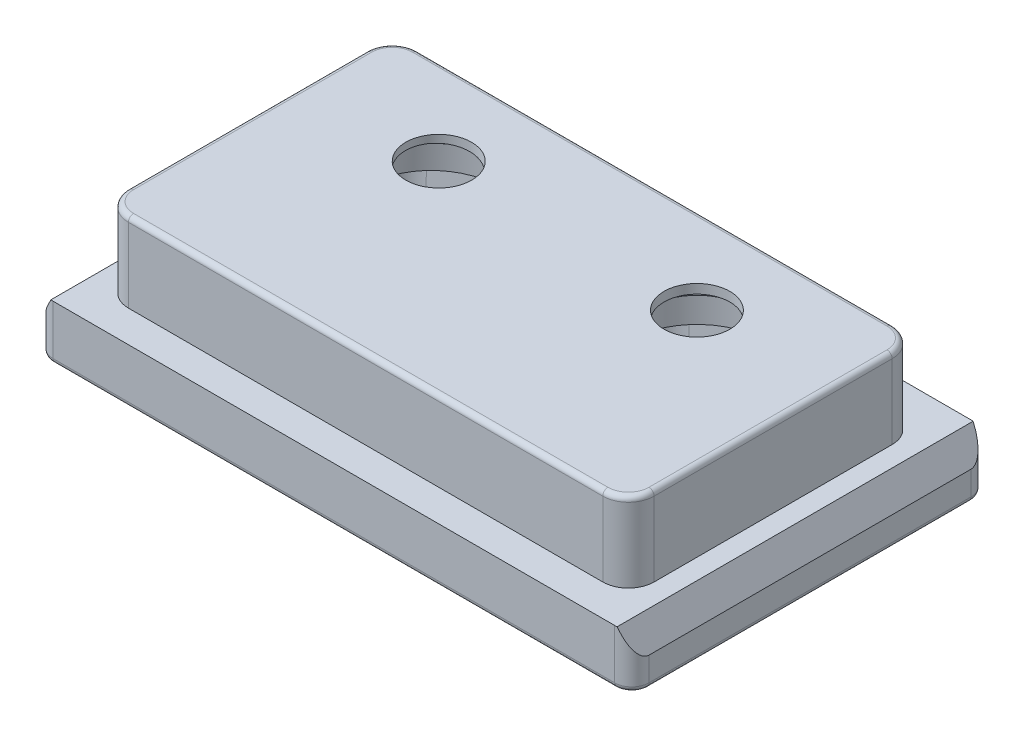
SolidWorks part; units mm, degrees
ref_plane "Front Plane" through (0, 0, 0) normal (0, 0, 1) x (1, 0, 0)
ref_plane "Top Plane" through (0, 0, 0) normal (0, 1, 0) x (1, 0, 0)
ref_plane "Right Plane" through (0, 0, 0) normal (1, 0, 0) x (0, 0, -1)
sketch "Sketch1" plane through (0, 0, 0) normal (0, 1, 0) x (1, 0, 0)
  line L1 (41.656, -26.416) -> (-41.656, -26.416)
  line L2 (44.196, -23.876) -> (44.196, 23.876)
  line L3 (41.656, 26.416) -> (-41.656, 26.416)
  line L4 (-44.196, -23.876) -> (-44.196, 23.876)
  line L5 (44.196, -26.416) -> (-44.196, 26.416) construction
  line L6 (44.196, 26.416) -> (-44.196, -26.416) construction
  arc A0 (-41.656, -26.416) -> (-44.196, -23.876) centre (-41.656, -23.876) cw
  arc A1 (41.656, -26.416) -> (44.196, -23.876) centre (41.656, -23.876) ccw
  arc A2 (44.196, 23.876) -> (41.656, 26.416) centre (41.656, 23.876) ccw
  arc A3 (-41.656, 26.416) -> (-44.196, 23.876) centre (-41.656, 23.876) ccw
  point P0 (0, 0)
  dimension "D3" = 2.54
  dimension "D1" = 52.832
  dimension "D2" = 88.392
extrude "Boss-Extrude1" add sketch "Sketch1" along normal blind 8.128
fillet "Fillet1" radius 0.762 8 edges at (-43.4521, 0, 25.6721) (-44.196, 0, 0) (-43.4521, 0, -25.6721) (0, 0, -26.416) (43.4521, 0, -25.6721) (44.196, 0, 0) (43.4521, 0, 25.6721) (0, 0, 26.416)
chamfer "Chamfer1" distance 3.81 angle 30 2 edges at (44.196, 8.128, 0) (-44.196, 8.128, 0) tangent propagation no first distance on face at (44.196, 4.445, 0) first distance on face at (-44.196, 4.445, 0)
sketch "Sketch2" plane through (0, 8.128, 0) normal (0, 1, 0) x (1, 0, 0)
  line L0 (44.196, 23.876) -> (44.196, -23.876) construction
  line L1 (-35.179, 21.209) -> (35.179, 21.209)
  line L2 (-38.989, 17.399) -> (-38.989, -17.907)
  line L3 (-35.179, -21.717) -> (35.179, -21.717)
  line L4 (38.989, 17.399) -> (38.989, -17.907)
  line L5 (-41.656, -26.416) -> (41.656, -26.416) construction
  arc A0 (35.179, 21.209) -> (38.989, 17.399) centre (35.179, 17.399) cw
  arc A1 (35.179, -21.717) -> (38.989, -17.907) centre (35.179, -17.907) ccw
  arc A2 (-38.989, -17.907) -> (-35.179, -21.717) centre (-35.179, -17.907) ccw
  arc A3 (-35.179, 21.209) -> (-38.989, 17.399) centre (-35.179, 17.399) ccw
  dimension "D5" = 3.81
  dimension "D1" = 42.926
  dimension "D2" = 77.978
  dimension "D3" = 5.207
  dimension "D4" = 4.699
extrude "Boss-Extrude2" add sketch "Sketch2" along normal blind 11.7856
fillet "Fillet2" radius 0.762 8 edges at (-38.989, 19.9136, 0.254) (-37.8731, 19.9136, -20.0931) (0, 19.9136, -21.209) (37.8731, 19.9136, -20.0931) (38.989, 19.9136, 0.254) (37.8731, 19.9136, 20.6011) (0, 19.9136, 21.717) (-37.8731, 19.9136, 20.6011)
sketch "Sketch3" plane through (0, 8.128, 0) normal (0, 1, 0) x (1, 0, 0)
  line L0 (-38.989, 17.399) -> (-38.989, -17.907) construction
  line L1 (-38.989, -9.5758) -> (-40.513, -9.5758)
  line L2 (-38.989, -9.5758) -> (-38.989, 8.5598)
  line L3 (-38.989, 8.5598) -> (-40.513, 8.5598)
  line L4 (-40.513, -9.5758) -> (-40.513, 8.5598)
  line L5 (35.179, 21.209) -> (-35.179, 21.209) construction
  dimension "D1" = 1.524
  dimension "D3" = 18.1356
  dimension "D2" = 12.6492
extrude "Boss-Extrude3" add sketch "Sketch3" along normal blind 6.35
sketch "Sketch4" plane through (0, 14.478, 0) normal (0, 1, 0) x (1, 0, 0)
  line L0 (-40.513, 8.5598) -> (-40.513, -9.5758) construction
  line L1 (-38.989, -9.5758) -> (-38.989, 8.5598) construction
  line L2 (-41.9963, -9.5758) -> (-41.9963, 8.5598) construction
  line L3 (-41.9963, 26.3931) -> (-41.9963, -26.3931) construction
  line L4 (-38.989, -9.5758) -> (-40.513, -9.5758)
  line L5 (-40.513, -9.5758) -> (-40.513, 8.5598)
  line L6 (-40.513, 8.5598) -> (-38.989, 8.5598)
  arc A0 (-38.989, 8.5598) -> (-40.513, 5.9438) centre (-41.9963, 8.5598) cw
  arc A1 (-38.989, -9.5758) -> (-40.513, -6.9598) centre (-41.9963, -9.5758) ccw
  line M3 (-38.989, 8.5598) -> (-40.513, 8.5598)
  line M4 (-40.513, 8.5598) -> (-40.513, -9.5758)
  line M5 (-40.513, -9.5758) -> (-38.989, -9.5758)
  dimension "D1" = 0
extrude "Cut-Extrude1" cut sketch "Sketch4" against normal up to surface (6.35 mm away) contours A1 M5 M4 | A0 M3 M4 region at (-39.8879, 14.478, -7.5344) region at (-39.8879, 14.478, 8.5504) up to face at (0, 8.128, 0)
fillet "Fillet3" radius 0.508 2 edges at (-40.513, 11.303, -5.9438) (-40.513, 11.303, 6.9598)
sketch "Sketch5" plane through (0, 0, 0) normal (0, -1, 0) x (1, 0, 0)
  line L0 (44.196, 23.876) -> (44.196, -23.876) construction
  line L1 (-32.385, -23.749) -> (32.385, -23.749)
  line L2 (-41.275, -14.859) -> (-41.275, 14.859)
  line L3 (-32.385, 23.749) -> (32.385, 23.749)
  line L4 (41.275, -14.859) -> (41.275, 14.859)
  line L6 (41.656, -26.416) -> (-41.656, -26.416) construction
  arc A0 (32.385, 23.749) -> (41.275, 14.859) centre (32.385, 14.859) cw
  arc A1 (32.385, -23.749) -> (41.275, -14.859) centre (32.385, -14.859) ccw
  arc A2 (-41.275, 14.859) -> (-32.385, 23.749) centre (-32.385, 14.859) cw
  arc A3 (-32.385, -23.749) -> (-41.275, -14.859) centre (-32.385, -14.859) cw
  point P12 (41.275, -23.749)
  point P17 (-41.275, -23.749)
  dimension "D5" = 8.89
  dimension "D1" = 82.55
  dimension "D2" = 2.921
  dimension "D3" = 47.498
  dimension "D4" = 2.667
extrude "Cut-Extrude2" cut sketch "Sketch5" against normal blind 3.048
fillet "Fillet4" radius 0.254 8 edges at (0, 0, -23.749) (-38.6712, 0, -21.1452) (-41.275, 0, 0) (-38.6712, 0, 21.1452) (0, 0, 23.749) (38.6712, 0, 21.1452) (41.275, 0, 0) (38.6712, 0, -21.1452)
sketch "Sketch6" plane through (0, 3.048, 0) normal (0, -1, 0) x (1, 0, 0)
  line L0 (44.196, -23.876) -> (44.196, 23.876) construction
  line L1 (41.656, -26.416) -> (-41.656, -26.416) construction
  circle A0 centre (0, -18.161) radius 1.1303
  circle A1 centre (0, 18.161) radius 1.1303
  circle A2 centre (-35.687, 2.159) radius 1.1303
  circle A3 centre (35.687, 2.159) radius 1.1303
  dimension "D7" = 2.2606
  dimension "D8" = 2.2606
  dimension "D9" = 2.2606
  dimension "D10" = 2.2606
  dimension "D1" = 35.687
  dimension "D2" = 35.687
  dimension "D3" = 8.509
  dimension "D4" = 20.32
  dimension "D5" = 16.002
  dimension "D6" = 8.255
extrude "Cut-Extrude3" cut sketch "Sketch6" against normal blind 10.16
sketch "Sketch7" plane through (0, 19.9136, 0) normal (0, 1, 0) x (1, 0, 0)
  line L0 (-35.179, 21.209) -> (35.179, 21.209) construction
  line L1 (38.989, 17.399) -> (38.989, -17.907) construction
  circle A0 centre (19.05, 8.382) radius 4.8768
  dimension "D3" = 9.7536
  dimension "D1" = 12.827
  dimension "D2" = 19.939
extrude "Cut-Extrude4" cut sketch "Sketch7" against normal through all
ref_plane "Plane1" through (-19.2532, 0, 0) normal (1, 0, 0) x (0, 0, -1)
ref_axis "Axis1" through (-19.2532, 19.9136, 20.955) along (0, 0, -1)
ref_plane "Plane2" through (0.9413, 18.9083, 0) normal (0.0497, 0.9988, 0) x (0, 0, -1)
sketch "Sketch8" plane through (0.9413, 18.9083, 0) normal (0.0497, 0.9988, 0) x (0, 0, -1)
  line L0 (21.209, 36.0877) -> (21.209, -34.1832) construction
  line L1 (-20.955, 20.2195) -> (20.447, 20.2195) construction
  circle A0 centre (8.382, 20.2195) radius 4.8768
  dimension "D3" = 9.7536
  dimension "D1" = 12.827
  dimension "D2" = 0
extrude "Cut-Extrude5" cut sketch "Sketch8" against normal through all and the other way blind 10.16
ref_plane "Plane3" through (0.4879, 9.8009, 0) normal (0.0497, 0.9988, 0) x (0, 0, -1)
sketch "Sketch9" plane through (0.4879, 9.8009, 0) normal (0.0497, 0.9988, 0) x (0, 0, -1)
  line L0 (3.5558, 5.4049) -> (-8.7689, 12.5206)
  line L1 (16.129, 35.4595) -> (5.1433, 35.4595)
  line L2 (19.304, 32.2845) -> (19.304, 8.1545)
  line L3 (16.129, 4.9795) -> (5.1433, 4.9795)
  line L4 (5.1433, 4.9795) -> (3.4419, 4.9795) construction
  line L5 (3.5558, 35.0341) -> (-8.7689, 27.9185)
  line L6 (3.5558, 5.4049) -> (4.2926, 4.9795) construction
  line L7 (5.1433, 35.4595) -> (3.8888, 35.4595) construction
  line L8 (3.5558, 35.0341) -> (4.2926, 35.4595) construction
  circle A0 centre (8.382, 20.2195) radius 4.8768 construction
  arc A1 (-8.7689, 27.9185) -> (-8.7689, 12.5206) centre (-4.3239, 20.2195) ccw
  arc A2 (3.5558, 35.0341) -> (5.1433, 35.4595) centre (5.1433, 32.2845) cw
  arc A3 (3.5558, 5.4049) -> (5.1433, 4.9795) centre (5.1433, 8.1545) ccw
  arc A4 (19.304, 8.1545) -> (16.129, 4.9795) centre (16.129, 8.1545) cw
  arc A5 (16.129, 35.4595) -> (19.304, 32.2845) centre (16.129, 32.2845) cw
  dimension "D6" = 8.89
  dimension "D5" = 3.175
  dimension "D1" = 30.48
  dimension "D2" = 15.24
  dimension "D3" = 10.922
  dimension "D4" = 15.0114
  dimension "D7" = 60
  dimension "D8" = 30
  dimension "D9" = 15.0114
extrude "Cut-Extrude6" cut sketch "Sketch9" against normal blind 10.16
sketch "Sketch10" plane through (0.4879, 9.8009, 0) normal (-0.0497, -0.9988, 0) x (0.9988, -0.0497, 0)
  circle A0 centre (-20.2195, -8.382) radius 6.8326
  dimension "D1" = 13.6652
extrude "Cut-Extrude7" cut sketch "Sketch10" against normal blind 7.7724
sketch "Sketch11" plane through (0.4879, 9.8009, 0) normal (-0.0497, -0.9988, 0) x (0.9988, -0.0497, 0)
  circle A0 centre (-20.2195, -8.382) radius 7.2517
  dimension "D1" = 14.5034
extrude "Cut-Extrude8" cut sketch "Sketch11" against normal blind 6.7818
sketch "Sketch12" plane through (0.4879, 9.8009, 0) normal (-0.0497, -0.9988, 0) x (0.9988, -0.0497, 0)
  circle A0 centre (-20.2195, -8.382) radius 9.2329
  dimension "D1" = 18.4658
extrude "Cut-Extrude9" cut sketch "Sketch12" against normal blind 5.9436
sketch "Sketch13" plane through (0.4879, 9.8009, 0) normal (-0.0497, -0.9988, 0) x (0.9988, -0.0497, 0)
  circle A0 centre (-20.2195, -8.382) radius 10.3632
  dimension "D1" = 20.7264
extrude "Cut-Extrude10" cut sketch "Sketch13" against normal blind 4.953
fillet "Fillet5" radius 0.254 2 edges at (-10.1896, 16.2835, -8.382) (-12.496, 18.2293, -8.382)
sketch "Sketch14" plane through (0, 3.048, 0) normal (0, -1, 0) x (1, 0, 0)
  line L0 (19.05, -8.382) -> (19.05, 4.5223) construction
  line L1 (6.985, -19.304) -> (31.115, -19.304)
  line L2 (3.81, -16.129) -> (3.81, -5.1323)
  line L3 (3.81, -4.2926) -> (34.29, -4.2926)
  line L4 (34.29, -16.129) -> (34.29, -5.1323)
  line L5 (11.3222, 8.917) -> (4.2251, -3.5627)
  line L6 (26.7778, 8.917) -> (33.8749, -3.5627)
  circle A0 centre (19.05, -8.382) radius 4.8768 construction
  circle A1 centre (19.05, 4.5223) radius 8.89
  arc A2 (33.8749, -3.5627) -> (34.29, -5.1323) centre (31.115, -5.1323) cw
  arc A3 (31.115, -19.304) -> (34.29, -16.129) centre (31.115, -16.129) ccw
  arc A4 (6.985, -19.304) -> (3.81, -16.129) centre (6.985, -16.129) cw
  arc A5 (3.81, -5.1323) -> (4.2251, -3.5627) centre (6.985, -5.1323) cw
  point P17 (34.29, -19.304)
  point P20 (3.81, -19.304)
  circle M15 centre (19.05, -8.382) radius 4.8768
  dimension "D6" = 17.78
  dimension "D7" = 3.175
  dimension "D1" = 15.0114
  dimension "D2" = 30.48
  dimension "D3" = 15.24
  dimension "D4" = 10.922
  dimension "D5" = 59.253
extrude "Cut-Extrude11" cut sketch "Sketch14" against normal blind 7.7216 contours A2 L6 A1 L3 M15 | A1 M15 | A5 L2 A4 L1 A3 L4 A2 L3 M15 | A5 L3 A1 L5 M15 region at (4.9802, 3.048, -18.1338) region at (9.3036, 3.048, -1.0374) region at (28.7964, 3.048, -1.0374) region at (19.05, 3.048, 4.6136)
sketch "Sketch15" plane through (0, 10.7696, 0) normal (0, -1, 0) x (1, 0, 0)
  circle A0 centre (19.05, -8.382) radius 6.8326
  dimension "D1" = 13.6652
extrude "Cut-Extrude12" cut sketch "Sketch15" against normal blind 7.7724
sketch "Sketch16" plane through (0, 10.7696, 0) normal (0, -1, 0) x (1, 0, 0)
  circle A0 centre (19.05, -8.382) radius 7.2517
  dimension "D1" = 14.5034
extrude "Cut-Extrude13" cut sketch "Sketch16" against normal blind 6.7818
sketch "Sketch17" plane through (0, 10.7696, 0) normal (0, -1, 0) x (1, 0, 0)
  circle A0 centre (19.05, -8.382) radius 9.2329
  dimension "D1" = 18.4658
extrude "Cut-Extrude14" cut sketch "Sketch17" against normal blind 5.9436
sketch "Sketch18" plane through (0, 10.7696, 0) normal (0, -1, 0) x (1, 0, 0)
  circle A0 centre (19.05, -8.382) radius 10.3632
  dimension "D1" = 20.7264
extrude "Cut-Extrude15" cut sketch "Sketch18" against normal blind 4.953
fillet "Fillet6" radius 0.254 2 edges at (19.05, 16.7132, -17.6149) (19.05, 18.542, -15.2146)
sketch "Sketch19" plane through (0.4879, 9.8009, 0) normal (-0.0497, -0.9988, 0) x (0.9988, -0.0497, 0)
  line L0 (-20.2195, -8.382) -> (-20.2195, 4.318) construction
  line L1 (-20.2195, 4.318) -> (-31.218, -14.732)
  line L2 (-31.218, -14.732) -> (-9.221, -14.732)
  line L3 (-9.221, -14.732) -> (-20.2195, 4.318)
  circle A0 centre (-20.2195, -8.382) radius 6.35 construction
  circle A1 centre (-20.2195, 4.318) radius 1.5
  circle A2 centre (-31.218, -14.732) radius 1.5
  circle A3 centre (-9.221, -14.732) radius 1.5
  dimension "D2" = 3
  dimension "D1" = 12.7
extrude "Cut-Extrude16" cut sketch "Sketch19" against normal blind 6.604 contours L1 A2 L2 | L2 A2 L1 | L2 A3 L3 | L3 A3 L2 | L3 A1 L1 | L1 A1 L3 region at (-19.7066, 10.8063, 3.3631) region at (-19.7066, 10.8063, 4.509) region at (-29.8655, 11.312, -14.2545) region at (-30.8567, 11.3614, -14.8275) region at (-8.5565, 10.2512, -14.8275) region at (-9.5476, 10.3005, -14.2545)
sketch "Sketch20" plane through (0, 10.7696, 0) normal (0, -1, 0) x (1, 0, 0)
  line L0 (19.05, -8.382) -> (19.05, 4.318) construction
  line L1 (19.05, 4.318) -> (8.0515, -14.732)
  line L2 (8.0515, -14.732) -> (30.0485, -14.732)
  line L3 (30.0485, -14.732) -> (19.05, 4.318)
  circle A0 centre (19.05, -8.382) radius 6.35 construction
  circle A1 centre (8.0515, -14.732) radius 1.5
  circle A2 centre (19.05, 4.318) radius 1.5
  circle A3 centre (30.0485, -14.732) radius 1.5
  dimension "D2" = 3
  dimension "D1" = 12.7
extrude "Cut-Extrude17" cut sketch "Sketch20" against normal blind 6.604 contours L2 A1 L1 | L1 A1 L2 | L3 A2 L1 | L1 A2 L3 | L3 A3 L2 | L2 A3 L3 region at (19.05, 10.7696, 3.3631) region at (19.05, 10.7696, 4.509) region at (8.8785, 10.7696, -14.2545) region at (7.8861, 10.7696, -14.8275) region at (30.2139, 10.7696, -14.8275) region at (29.2215, 10.7696, -14.2545)
